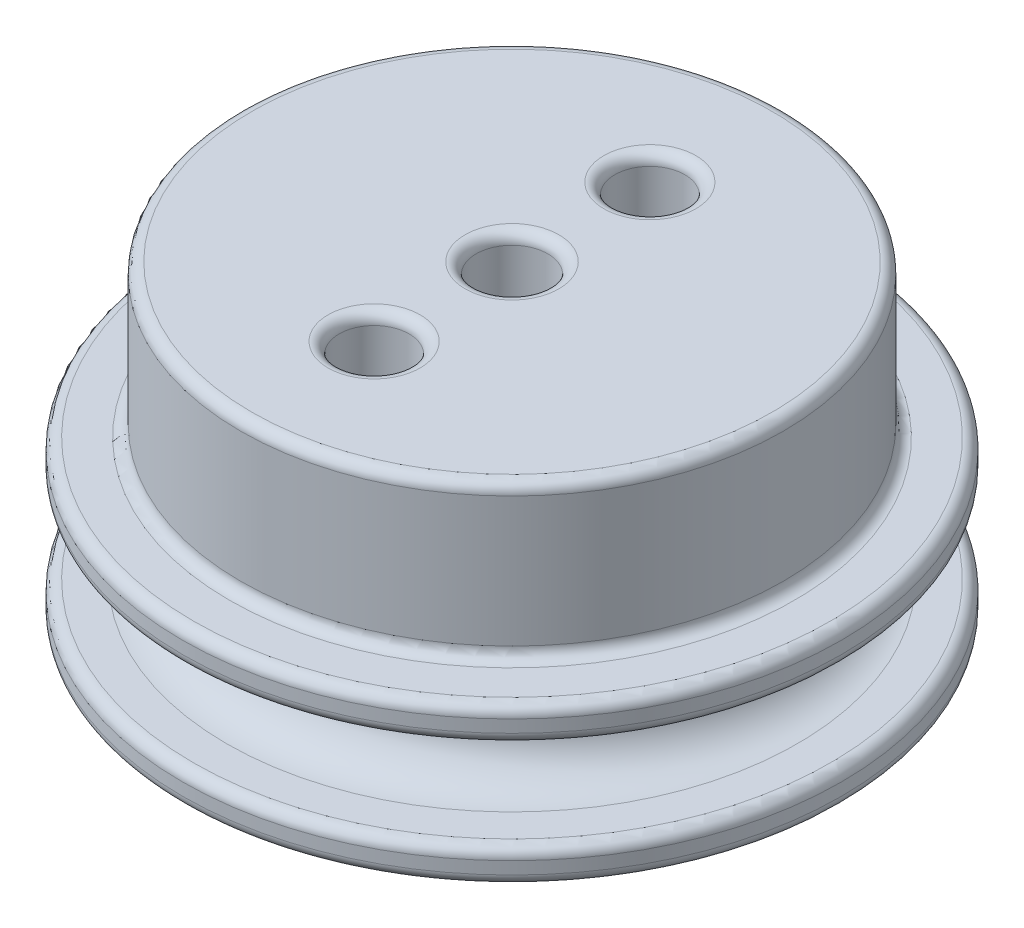
SolidWorks part; units mm, degrees
ref_plane "Front Plane" through (0, 0, 0) normal (0, 0, 1) x (1, 0, 0)
ref_plane "Top Plane" through (0, 0, 0) normal (0, 1, 0) x (1, 0, 0)
ref_plane "Right Plane" through (0, 0, 0) normal (1, 0, 0) x (0, 0, -1)
ref_axis "Axis1" through (0, 10.9123, 0) along (0, -1, 0)
sketch "Sketch1" plane through (0, 0, 0) normal (0, 0, 1) x (1, 0, 0)
  line L0 (-15.1765, -3.6195) -> (0, -3.6195)
  line L1 (0, -3.6195) -> (0, 3.6195) construction
  line L2 (-15.1765, 3.6195) -> (0, 3.6195) construction
  line L3 (-13.1445, -2.032) -> (-15.1765, -2.032)
  line L4 (-15.1765, -2.032) -> (-15.1765, -3.6195)
  line L5 (-13.1445, 2.032) -> (-15.1765, 2.032)
  line L6 (-15.1765, 2.032) -> (-15.1765, 3.6195)
  line L7 (-15.1765, 3.6195) -> (-12.5, 3.6195)
  line L8 (-12.5, 3.6195) -> (-12.5, 10.6195)
  line L9 (-12.5, 10.6195) -> (0, 10.6195)
  line L14 (0, 10.6195) -> (0, -3.6195)
  arc A0 (-13.1445, 2.032) -> (-13.1445, -2.032) centre (-13.1445, 0) cw
  circle A1 centre (-12.7, 0) radius 1.5875 construction
  circle A4 centre (-13.1445, 0) radius 2.032 construction
  point P3 (-13.0949, 0)
  point P7 (0, 0)
  point P18 (-12.9161, 2.032)
  point P19 (0, 0)
  dimension "D1" = 4.064
  dimension "D2" = 3.175
  dimension "D3" = 1.5875
  dimension "D4" = 7
  dimension "D5" = 25
  dimension "D6" = 12.7
revolve "Revolve1" add sketch "Sketch1" angle 360 about L14
sketch "Sketch2" plane through (0, 10.6195, 0) normal (0, 1, 0) x (1, 0, 0)
  line L0 (0, 6.35) -> (0, -6.35) construction
  circle A2 centre (0, 6.35) radius 1.6129
  circle A3 centre (0, 0) radius 1.651
  circle A4 centre (0, -6.35) radius 1.6129
  point P7 (0, 0)
  dimension "D2" = 12.7
  dimension "D3" = 3.2258
  dimension "D1" = 3.302
extrude "Cut-Extrude1" cut sketch "Sketch2" against normal blind 7.62
sketch "Sketch3" plane through (0, 2.9995, 0) normal (0, 1, 0) x (1, 0, 0)
  circle A0 centre (0, 0) radius 2.921
  dimension "D1" = 5.842
extrude "Cut-Extrude2" cut sketch "Sketch3" against normal through all
fillet "Fillet1" radius 0.508 10 edges at (0, 10.6195, 12.5) (0, 10.6195, 7.9629) (0, 10.6195, 1.651) (0, 10.6195, -4.7371) (0, 3.6195, 12.5) (0, 3.6195, 15.1765) (0, -3.6195, 15.1765) (0, -3.6195, 2.921) (0, -2.032, 15.1765) (0, 2.032, 15.1765)
